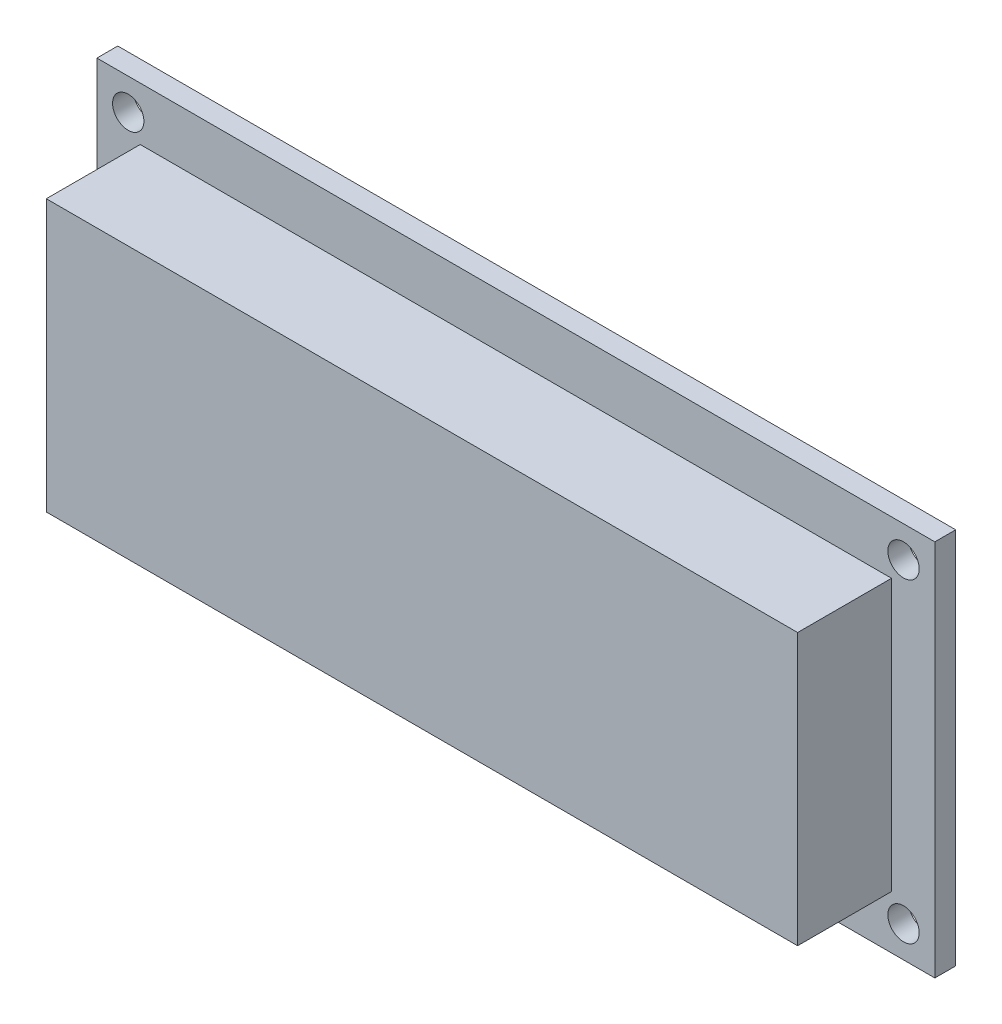
SolidWorks part; units mm, degrees
ref_plane "Спереди" through (0, 0, 0) normal (0, 0, 1) x (1, 0, 0)
ref_plane "Сверху" through (0, 0, 0) normal (0, 1, 0) x (1, 0, 0)
ref_plane "Справа" through (0, 0, 0) normal (1, 0, 0) x (0, 0, -1)
sketch "Эскиз1" plane through (0, 0, 0) normal (0, 0, 1) x (1, 0, 0)
  line L1 (-19.0452, 13.6248) -> (61.2548, 13.6248)
  line L2 (-19.0452, 13.6248) -> (-19.0452, -22.5752)
  line L3 (-19.0452, -22.5752) -> (61.2548, -22.5752)
  line L4 (61.2548, 13.6248) -> (61.2548, -22.5752)
  dimension "D1" = 80.3
  dimension "D2" = 36.2
extrude "Бобышка-Вытянуть1" add sketch "Эскиз1" along normal blind 2
sketch "Эскиз2" plane through (0, 0, 2) normal (0, 0, 1) x (1, 0, 0)
  line L0 (61.2548, 13.6248) -> (-19.0452, 13.6248) construction
  line L1 (-14.8952, 8.5248) -> (57.1048, 8.5248)
  line L2 (-14.8952, 8.5248) -> (-14.8952, -17.4752)
  line L3 (-14.8952, -17.4752) -> (57.1048, -17.4752)
  line L4 (57.1048, 8.5248) -> (57.1048, -17.4752)
  line L8 (61.2548, -22.5752) -> (61.2548, 13.6248) construction
  point P8 (-50.8691, 27.0509)
  dimension "D1" = 72
  dimension "D2" = 26
  dimension "D3" = 5.1
  dimension "D4" = 4.15
extrude "Бобышка-Вытянуть2" add sketch "Эскиз2" along normal blind 9
sketch "Эскиз3" plane through (0, 0, 2) normal (0, 0, 1) x (1, 0, 0)
  line L0 (61.2548, -22.5752) -> (61.2548, 13.6248) construction
  line L1 (-19.0452, -22.5752) -> (61.2548, -22.5752) construction
  line L2 (61.2548, 13.6248) -> (-19.0452, 13.6248) construction
  line L3 (-19.0452, 13.6248) -> (-19.0452, -22.5752) construction
  circle A0 centre (-16.0452, 10.6248) radius 1.5
  circle A1 centre (58.2548, 10.6248) radius 1.5
  circle A2 centre (58.2548, -19.5752) radius 1.5
  circle A3 centre (-16.0452, -19.5752) radius 1.5
  dimension "D1" = 3
  dimension "D2" = 3
  dimension "D4" = 3
  dimension "D5" = 3
  dimension "D6" = 3
  dimension "D7" = 3
  dimension "D8" = 3
  dimension "D9" = 3
  dimension "D10" = 3
  dimension "D11" = 3
  dimension "D12" = 3
  dimension "D3" = 3
extrude "Вырез-Вытянуть1" cut sketch "Эскиз3" against normal through all
equation "\"1б5\"=2.10104"
